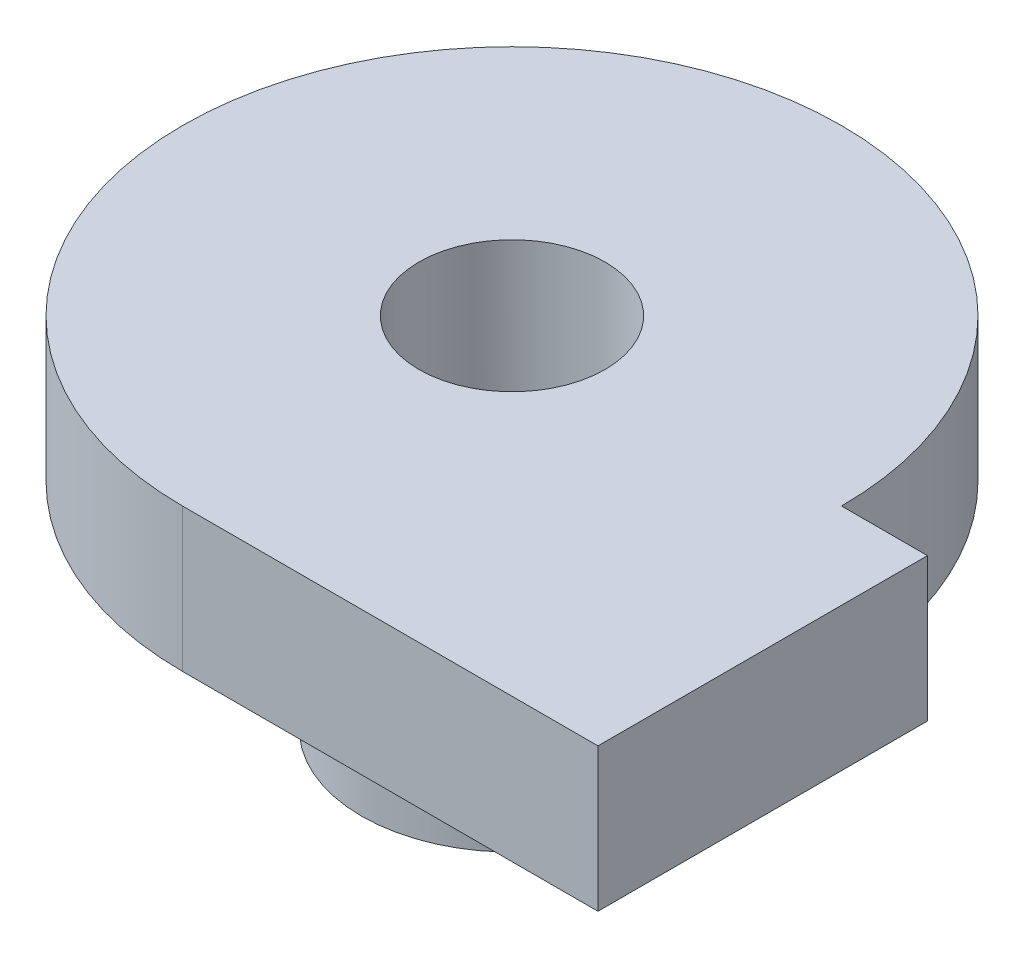
SolidWorks part; units mm, degrees
ref_plane "Front Plane" through (0, 0, 0) normal (0, 0, 1) x (1, 0, 0)
ref_plane "Top Plane" through (0, 0, 0) normal (0, 1, 0) x (1, 0, 0)
ref_plane "Right Plane" through (0, 0, 0) normal (1, 0, 0) x (0, 0, -1)
sketch "Sketch1" plane through (0, 0, 0) normal (0, 1, 0) x (1, 0, 0)
  circle A0 centre (0, 0) radius 11.5
  circle A1 centre (0, 0) radius 3.25
  dimension "D1" = 23
  dimension "D2" = 6.5
extrude "Boss-Extrude1" add sketch "Sketch1" along normal blind 5
sketch "Sketch5" plane through (0, 5, 0) normal (0, 1, 0) x (1, 0, 0)
  line L0 (0, -11.5) -> (14.5, -11.5)
  line L1 (14.5, -11.5) -> (14.5, 0)
  line L2 (14.5, 0) -> (10.8565, 0)
  line L3 (10.8565, 0) -> (0, -11.5)
  line L5 (-2.75, 0) -> (2.75, 0) construction
  line L6 (0, -2.75) -> (0, 2.75) construction
  circle A2 centre (0, 0) radius 11.5 construction
  dimension "D1" = 14.5
extrude "Boss-Extrude3" add sketch "Sketch5" against normal blind 5
sketch "Sketch6" plane through (0, 0, 0) normal (0, -1, 0) x (1, 0, 0)
  circle A0 centre (0, 0) radius 3.25
  circle A1 centre (0, 0) radius 5.25
  circle A2 centre (0, 0) radius 3.25 construction
  dimension "D1" = 2
extrude "Boss-Extrude4" add sketch "Sketch6" along normal blind 7.5
